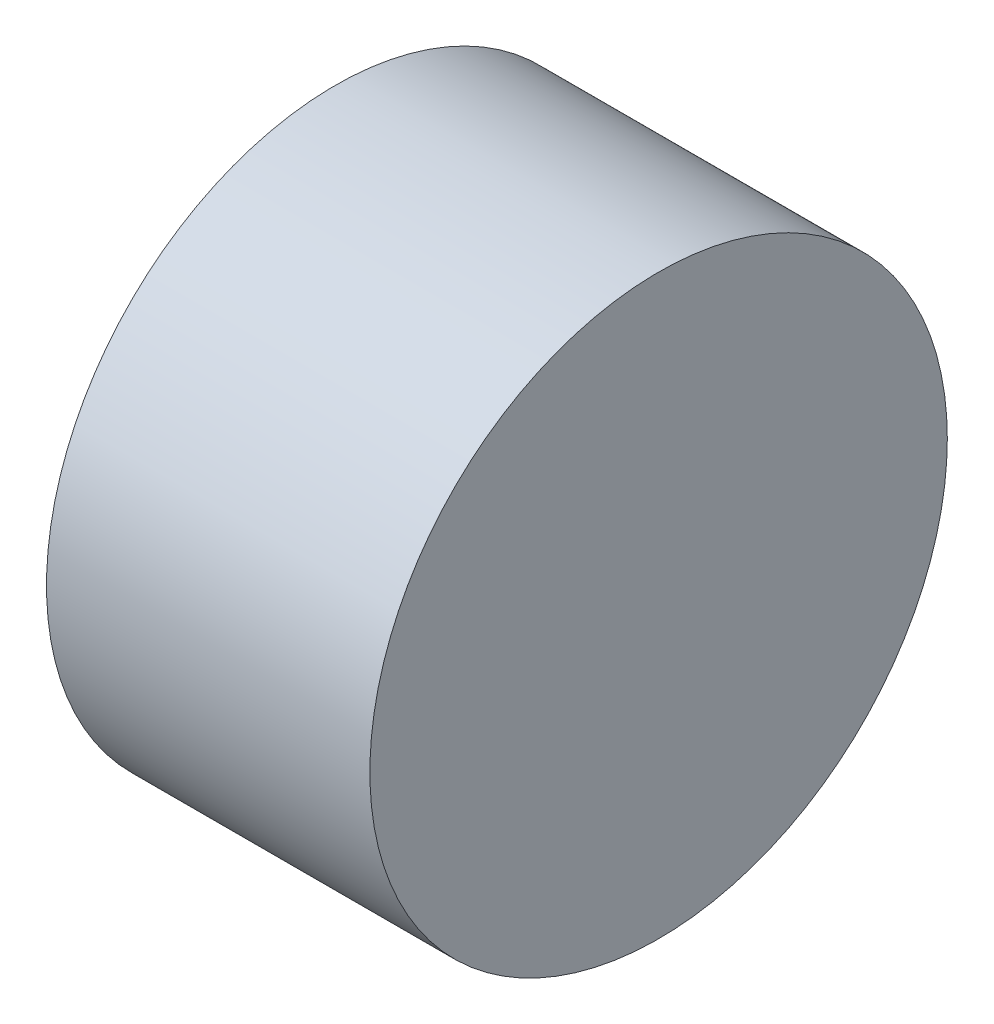
SolidWorks part; units mm, degrees
ref_plane "Front Plane" through (0, 0, 0) normal (0, 0, 1) x (1, 0, 0)
ref_plane "Top Plane" through (0, 0, 0) normal (0, 1, 0) x (1, 0, 0)
ref_plane "Right Plane" through (0, 0, 0) normal (1, 0, 0) x (0, 0, -1)
sketch "Sketch1" plane through (0, 0, 0) normal (1, 0, 0) x (0, 0, -1)
  circle A0 centre (0, 0) radius 5
  dimension "D1" = 10
extrude "Boss-Extrude1" add sketch "Sketch1" along normal blind 5.6
ref_plane "Plane1" through (0, 0, 0) normal (0, 1, 0) x (1, 0, 0)
